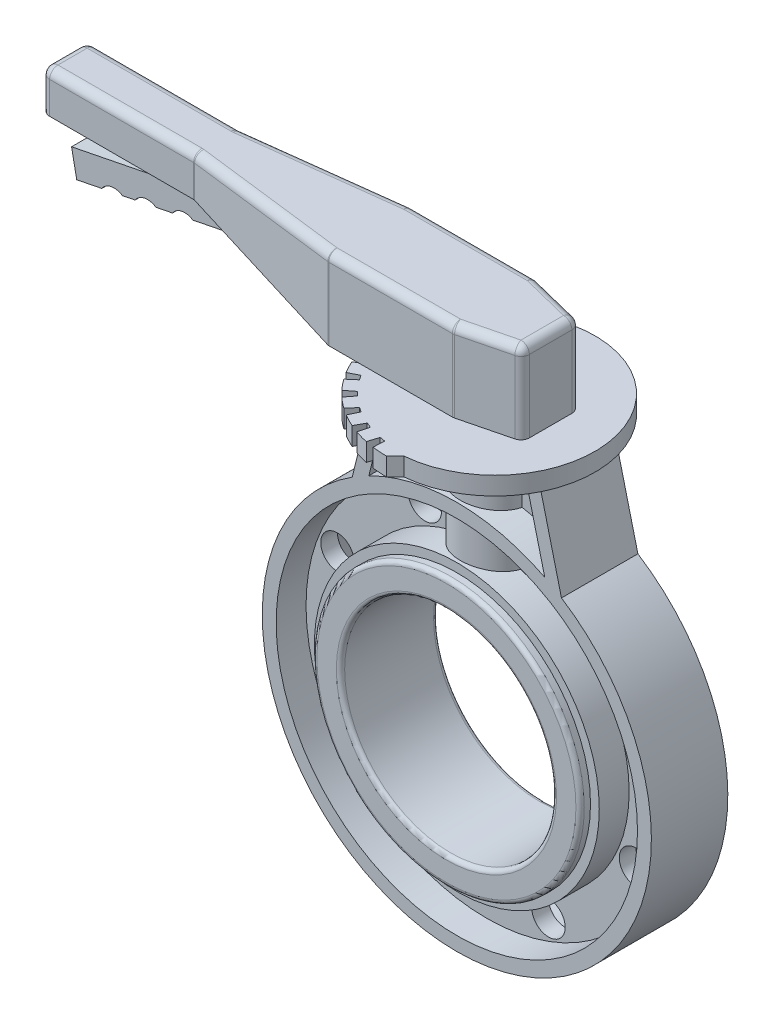
SolidWorks part; units mm, degrees
note: '?' marks a value the reader was unsure of. The reader was unsure of these and kept them because the rebuilt part matched: shared geometry of "Sketch5<3>".
material "PVC Rigid"
ref_plane "Front Plane" through (0, 0, 0) normal (0, 0, 1) x (1, 0, 0)
ref_plane "Top Plane" through (0, 0, 0) normal (0, 1, 0) x (1, 0, 0)
ref_plane "Right Plane" through (0, 0, 0) normal (1, 0, 0) x (0, 0, -1)
sketch "Sketch1" plane through (0, 0, 0) normal (1, 0, 0) x (0, 0, -1)
  line L0 (-35, 0) -> (35, 0) construction
  line L1 (-27.5, 82.5) -> (27.5, 82.5)
  line L2 (27.5, 82.5) -> (27.5, 102.5)
  line L3 (27.5, 102.5) -> (6, 102.5)
  line L4 (6, 102.5) -> (6, 130)
  line L5 (6, 130) -> (27.5, 130)
  line L6 (27.5, 130) -> (27.5, 140)
  line L7 (27.5, 140) -> (-27.5, 140)
  line L8 (-27.5, 140) -> (-27.5, 130)
  line L9 (-27.5, 130) -> (-6, 130)
  line L10 (-6, 130) -> (-6, 102.5)
  line L11 (-6, 102.5) -> (-27.5, 102.5)
  line L12 (-27.5, 102.5) -> (-27.5, 82.5)
  line L13 (-6, 116.25) -> (6, 116.25) construction
  line L14 (0, 116.25) -> (0, 0) construction
  point P17 (-27.5, 135)
  dimension "D1" = 20
  dimension "T" = 70
  dimension "PCV ID" = 165
  dimension "OD" = 280
  dimension "OD_ringT" = 10
  dimension "Web_T" = 12
  dimension "PVC-T" = 55
revolve "Revolve1" add sketch "Sketch1" angle 360 about L0
sketch "Sketch2" plane through (0, 0, 0) normal (1, 0, 0) x (0, 0, -1)
  line L0 (-35, 0) -> (35, 0) construction
  line L1 (-27.5, 96.2) -> (-27.5, 82.5)
  line L2 (-27.5, 102.5) -> (-27.5, 82.5) construction
  line L3 (-27.5, 82.5) -> (27.5, 82.5)
  line L4 (27.5, 82.5) -> (27.5, 96.2)
  line L5 (27.5, 82.5) -> (27.5, 102.5) construction
  line L6 (27.5, 96.2) -> (35, 96.2)
  line L7 (35, 96.2) -> (35, 76.2)
  line L8 (35, 76.2) -> (-35, 76.2)
  line L9 (-35, 76.2) -> (-35, 96.2)
  line L10 (-35, 96.2) -> (-27.5, 96.2)
  dimension "D1" = 152.4
  dimension "D2" = 20
revolve "Revolve2" add sketch "Sketch2" angle 360 about L0
sketch "Sketch3" plane through (0, 0, 0) normal (0, 0, -1) x (-1, 0, 0)
  line L0 (0, 102.5) -> (0, 130) construction
  line L1 (44.4869, -107.401) -> (107.401, -44.4869) construction
  line L2 (107.401, -44.4869) -> (107.401, 44.4869) construction
  line L3 (107.401, 44.4869) -> (44.4869, 107.401) construction
  line L4 (44.4869, 107.401) -> (-44.4869, 107.401) construction
  line L5 (-44.4869, 107.401) -> (-107.401, 44.4869) construction
  line L6 (-107.401, 44.4869) -> (-107.401, -44.4869) construction
  line L7 (-107.401, -44.4869) -> (-44.4869, -107.401) construction
  line L8 (-44.4869, -107.401) -> (44.4869, -107.401) construction
  line L9 (0, 0) -> (0, 181) construction
  circle A0 centre (0, 0) radius 107.401 construction
  circle A1 centre (0, 0) radius 116.25 construction
  circle A2 centre (44.4869, -107.401) radius 12
  circle A3 centre (107.401, -44.4869) radius 12
  circle A4 centre (107.401, 44.4869) radius 12
  circle A5 centre (44.4869, 107.401) radius 12
  circle A6 centre (-44.4869, 107.401) radius 12
  circle A7 centre (-107.401, 44.4869) radius 12
  circle A8 centre (-107.401, -44.4869) radius 12
  circle A9 centre (-44.4869, -107.401) radius 12
  point P14 (0, 116.25)
  dimension "hd" = 24
  dimension "H1" = 181
extrude "Cut-Extrude1" cut sketch "Sketch3" against normal through all both and the other way through all
ref_plane "Plane1" through (0, 181, 0) normal (0, 1, 0) x (1, 0, 0)
sketch "Sketch5" plane through (0, 181, 0) normal (0, 1, 0) x (1, 0, 0)
  circle A0 centre (0, 0) radius 72
  circle A1 centre (0, 0) radius 25
  dimension "D1" = 144
  dimension "D2" = 50
extrude "Boss-Extrude1" add sketch "Sketch5" along normal blind 13 separate body contours A1 | A0 A1
extrude "Boss-Extrude2" add sketch "Sketch5<3>" against normal up to surface (78.5 mm away) separate body contours A1
sketch "Sketch5<3>" plane through (0, 181, 0) normal (0, 1, 0) x (1, 0, 0) same geometry as "Sketch5"
sketch "Sketch6" plane through (0, 0, 0) normal (0, 0, 1) x (1, 0, 0)
  line L0 (-52.8182, 187.5) -> (-70.5828, 116.25)
  line L2 (52.8182, 187.5) -> (70.5828, 116.25)
  line L3 (-72, 187.5) -> (72, 187.5) construction
  line L4 (-70.5828, 116.25) -> (70.5828, 116.25) construction
  line L5 (-72, 194) -> (-72, 181) construction
  line L6 (72, 181) -> (72, 194) construction
  line L7 (0, 102.5) -> (0, 130) construction
  circle A0 centre (0, 0) radius 136 construction
  circle A1 centre (0, 0) radius 140 construction
  point P12 (0, 116.25)
  dimension "D2" = 4
  dimension "D1" = 28
extrude "Extrude-Thin1" add sketch "Sketch6" along a picked direction on the side of the normal up to surface (27.5 mm away) and the other way up to surface (27.5 mm away) thin thin type mid plane wall 10
sketch "Sketch8" plane through (0, 0, 0) normal (0, 0, 1) x (1, 0, 0)
  line L0 (-49.2858, 181) -> (49.2858, 181)
  line L1 (49.2858, 181) -> (63.2771, 124.884)
  line L2 (-49.2858, 181) -> (-63.2771, 124.884)
  arc A0 (-63.2771, 124.884) -> (63.2771, 124.884) centre (0, 0) cw
extrude "Boss-Extrude3" add sketch "Sketch8" along normal mid plane 10
fillet "Fillet1" radius 3 4 edges at (76.2, 0, 35) (96.2, 0, 35) (76.2, 0, -35) (96.2, 0, -35)
sketch "Sketch9" plane through (0, 194, 0) normal (0, 1, 0) x (1, 0, 0)
  line L0 (0, 0) -> (0, -78) construction
  line L1 (0, 0) -> (-78, 0) construction
  line L2 (-78, 0) -> (-71.7261, 6.2739)
  line L3 (0, -78) -> (6.2739, -71.7261)
  line L4 (-55.1543, -55.1543) -> (0, 0) construction
  line L5 (-71.7261, 6.2739) -> (0, 0)
  line L6 (0, 0) -> (6.2739, -71.7261)
  arc A0 (-78, 0) -> (0, -78) centre (0, 0) ccw
  circle A1 centre (0, 0) radius 72 construction
  dimension "D1" = 156
extrude "Boss-Extrude4" add sketch "Sketch9" against normal up to surface (13 mm away) up to face at (0, 181, 72)
sketch "Sketch11" plane through (0, 194, 0) normal (0, 1, 0) x (1, 0, 0)
  line L0 (-10.4735, -77.2936) -> (-10.0902, -69.2978)
  line L1 (-10.0902, -69.2978) -> (-14.0304, -68.6087)
  line L2 (-14.0304, -68.6087) -> (-16.3838, -76.2599)
  line L3 (-12.0603, -68.9532) -> (0, 0) construction
  arc A0 (-78, 0) -> (0, -78) centre (0, 0) ccw construction
  arc A1 (-16.3838, -76.2599) -> (-10.4735, -77.2936) centre (0, 0) ccw
  dimension "D1" = 6
  dimension "D2" = 4
  dimension "D3" = 70
extrude "Cut-Extrude2" cut sketch "Sketch11" against normal up to next (13 mm away)
pattern_circular "CirPattern1" count 7 over 70 about axis through (0, 0, 0) along (0, 1, 0) of "Cut-Extrude2"
sketch "Sketch12" plane through (0, 194, 0) normal (0, 1, 0) x (1, 0, 0)
  line L0 (0, 30) -> (40, 20)
  line L1 (40, 20) -> (40, -20)
  line L2 (40, -20) -> (0, -30)
  line L4 (-90, -30) -> (-200, -16.5)
  line L5 (-200, -16.5) -> (-310, -16.5)
  line L6 (-310, -16.5) -> (-310, 16.5)
  line L7 (-310, 16.5) -> (-200, 16.5)
  line L10 (0, 0) -> (40, 0) construction
  line L11 (-200, 16.5) -> (-90, 30)
  line L12 (-310, 0) -> (0, 0) construction
  line L13 (-90, 30) -> (0, 30)
  line L14 (-90, -30) -> (0, -30)
  circle A0 centre (0, 0) radius 30 construction
  dimension "D4" = 60
  dimension "D1" = 33
  dimension "D2" = 110
  dimension "D3" = 40
  dimension "D5" = 40
  dimension "D6" = 310
  dimension "D7" = 90
extrude "Boss-Extrude5" add sketch "Sketch12" along normal blind 58 separate body
sketch "Sketch13" plane through (0, 0, 0) normal (0, 0, 1) x (1, 0, 0)
  line L0 (-310, 223) -> (-200, 223)
  line L1 (-310, 252) -> (-310, 194) construction
  line L2 (-200, 252) -> (-200, 194) construction
  line L3 (-200, 223) -> (-90, 194)
extrude "Cut-Extrude4" cut sketch "Sketch13" against normal through all both and the other way through all flip side to cut
sketch "Sketch14" plane through (0, 0, 0) normal (0, 0, 1) x (1, 0, 0)
  line L0 (-298.714, 201.4325) -> (-168.1249, 227.4397)
  line L1 (-168.1249, 227.4397) -> (-70.7365, 201.4325)
  line L2 (-70.7365, 201.4325) -> (-70.7365, 173.7653)
  line L3 (-70.7365, 173.7653) -> (-91.7635, 173.7653)
  line L4 (-91.7635, 173.7653) -> (-91.7635, 187.5989)
  line L5 (-91.7635, 187.5989) -> (-168.1249, 207.9909)
  line L6 (-168.1249, 207.9909) -> (-211.4854, 199.3555)
  line L7 (-294.9885, 182.7257) -> (-298.714, 201.4325)
  line L8 (-276.9688, 186.3143) -> (-294.9885, 182.7257)
  line L9 (-252.9805, 191.0917) -> (-262.0793, 189.2796)
  line L10 (-226.0875, 196.4475) -> (-238.0357, 194.068)
  line L11 (-268.0345, 180.3176) -> (-217.3267, 190.5715) construction
  arc A0 (-276.9688, 186.3143) -> (-262.0793, 189.2796) centre (-268.0345, 180.3176) cw
  arc A1 (-252.9805, 191.0917) -> (-238.0357, 194.068) centre (-244.0327, 185.1712) cw
  arc A2 (-226.0875, 196.4475) -> (-211.4854, 199.3555) centre (-217.3267, 190.5715) cw
  dimension "D7" = 10.7602
  dimension "D8" = 10.7292
  dimension "D9" = 10.5489
  dimension "D1" = 70.7365
  dimension "D2" = 21.0271
  dimension "D3" = 104.952
  dimension "D4" = 153.785
  dimension "D5" = 133.1536
  dimension "D6" = 100.8012
  dimension "D10" = 19.0742
  dimension "Lock-H" = 173.7653
  dimension "D12" = 18.3735
  dimension "D13" = 9.2775
  dimension "D14" = 12.1829
  dimension "D15" = 44.212
  dimension "D16" = 27.6672
  dimension "D17" = 79.0373
  dimension "D18" = 0.169
extrude "Boss-Extrude6" add sketch "Sketch14" along normal mid plane 12 separate body
fillet "Fillet2" radius 6 20 edges at (20, 252, -25) (40, 252, 0) (20, 252, 25) (-45, 252, 30) (-145, 252, 23.25) (-255, 252, 16.5) (-310, 252, 0) (-255, 252, -16.5) (-145, 252, -23.25) (-45, 252, -30) (-200, 237.5, 16.5) (-310, 237.5, 16.5) (-310, 237.5, -16.5) (-200, 237.5, -16.5) (-90, 223, -30) (0, 223, -30) (-90, 223, 30) (0, 223, 30) (40, 223, -20) (40, 223, 20)
other "CPoint1" parameters "Diameter"=152.4, "StubLength"=228.6
ref_axis "Axis1" through (0, 0, -45) along (0, 0, 1)?
other "CPoint2" parameters "Diameter"=152.4, "StubLength"=228.6
ref_axis "Axis2" through (0, 0, 45) along (0, 0, -1)?
other "RPoint1"
ref_axis "Vertical" through (0, 116.25, 0) along (0, -1, 0)?
